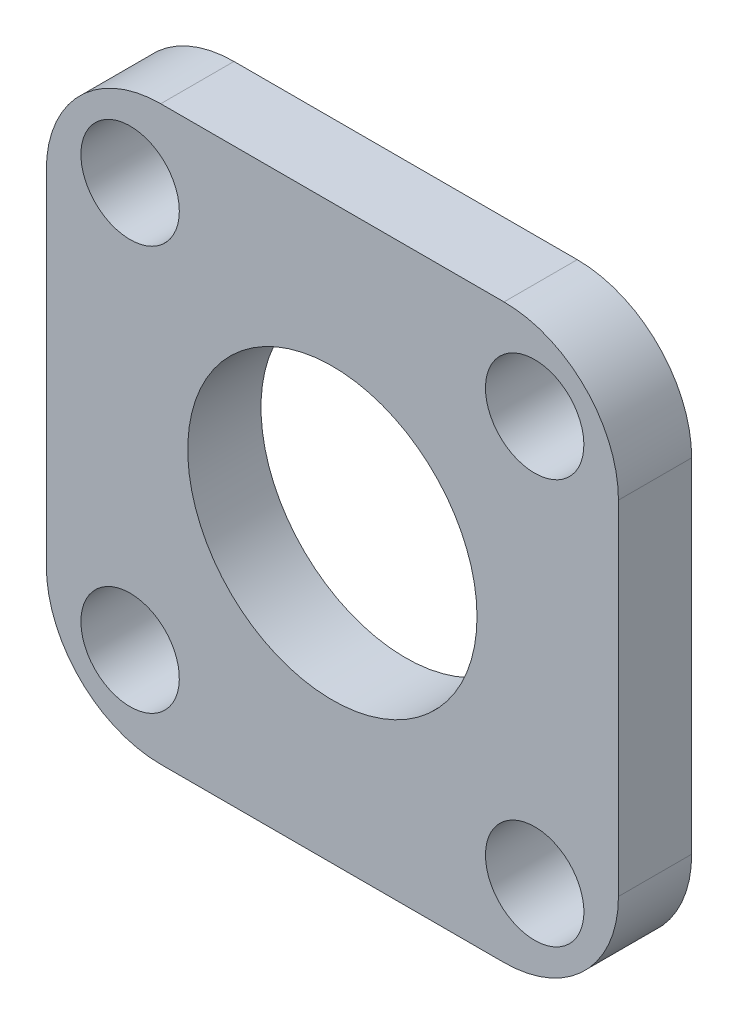
SolidWorks part; units mm, degrees
ref_plane "Front Plane" through (0, 0, 0) normal (0, 0, 1) x (1, 0, 0)
ref_plane "Top Plane" through (0, 0, 0) normal (0, 1, 0) x (1, 0, 0)
ref_plane "Right Plane" through (0, 0, 0) normal (1, 0, 0) x (0, 0, -1)
sketch "Sketch1" plane through (0, 0, 0) normal (0, 0, 1) x (1, 0, 0)
  line L1 (-12.5, 12.5) -> (12.5, 12.5)
  line L2 (-12.5, 12.5) -> (-12.5, -12.5)
  line L3 (-12.5, -12.5) -> (12.5, -12.5)
  line L4 (12.5, 12.5) -> (12.5, -12.5)
  line L5 (-12.5, 12.5) -> (12.5, -12.5) construction
  line L6 (-12.5, -12.5) -> (12.5, 12.5) construction
  point P0 (0, 0)
  dimension "D1" = 25
  dimension "D2" = 25
extrude "Boss-Extrude1" add sketch "Sketch1" along normal blind 3.2
sketch "Sketch2" plane through (0, 0, 3.2) normal (0, 0, 1) x (1, 0, 0)
  circle A0 centre (0, 0) radius 6.32
extrude "Cut-Extrude1" cut sketch "Sketch2" against normal up to next
sketch "Sketch3" plane through (0, 0, 3.2) normal (0, 0, 1) x (1, 0, 0)
  line L0 (-12.5, 12.5) -> (0, 0) construction
  circle A0 centre (-8.8388, 8.8388) radius 2.15
  dimension "D1" = 4.3
  dimension "D2" = 12.5
extrude "Cut-Extrude2" cut sketch "Sketch3" against normal through all
pattern_circular "CirPattern1" count 4 every 90 about axis through (0, 0, 3.2) along (0, 0, 1) of "Cut-Extrude2"
fillet "Fillet2" radius 5 4 edges at (-12.5, -12.5, 1.6) (12.5, -12.5, 1.6) (12.5, 12.5, 1.6) (-12.5, 12.5, 1.6)
